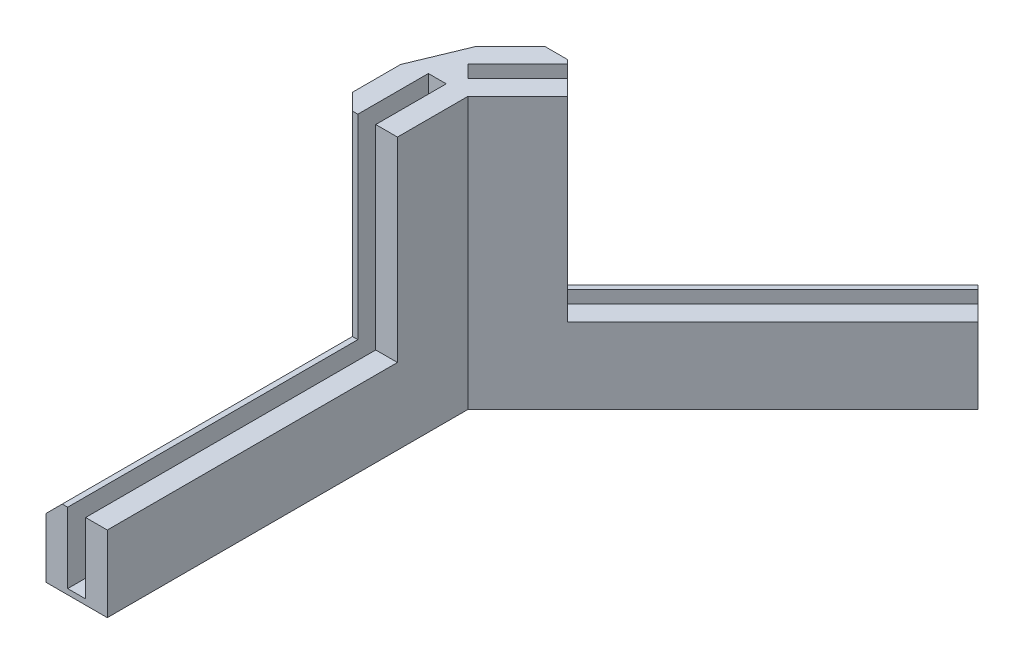
SolidWorks part; units mm, degrees
ref_plane "Front Plane" through (0, 0, 0) normal (0, 0, 1) x (1, 0, 0)
ref_plane "Top Plane" through (0, 0, 0) normal (0, 1, 0) x (1, 0, 0)
ref_plane "Right Plane" through (0, 0, 0) normal (1, 0, 0) x (0, 0, -1)
sketch "Sketch2" plane through (0, 0, 0) normal (0, 1, 0) x (1, 0, 0)
  line L0 (-1.7, -2) -> (-1.7, -15)
  line L1 (-1.7, -15) -> (-5.7, -15)
  line L2 (-5.7, -15) -> (-5.7, -2)
  line L3 (-5.7, -2) -> (-9, -2)
  line L4 (-9, -2) -> (-9, -15)
  line L5 (-9, -15) -> (-13, -15)
  line L7 (-13, -15) -> (-13, 2.6806)
  line L9 (-1.7, -2) -> (-13, 2.6806)
extrude "Boss-Extrude1" add sketch "Sketch2" along normal blind 50
sketch "Sketch3" plane through (0, 0, 2) normal (0, 0, 1) x (1, 0, 0)
  line L0 (-9, 0) -> (-9, 1)
  line L1 (-9, 50) -> (-9, 0) construction
  line L2 (-5.7, 0) -> (-5.7, 1)
  line L3 (-5.7, 50) -> (-5.7, 0) construction
  line L4 (-5.7, 1) -> (-9, 1)
  line L5 (-9, 0) -> (-5.7, 0)
extrude "Boss-Extrude2" add sketch "Sketch3" along normal up to vertex (13 mm away) up to point (-9, 0, 15)
sketch "Sketch5" plane through (0, 0, 15) normal (0, 0, 1) x (1, 0, 0)
  line L0 (-13, 0) -> (-1.7, 0)
  line L1 (-1.7, 50) -> (-1.7, 0) construction
  line L2 (-13, 0) -> (-1.7, 0) construction
  line L3 (-1.7, 0) -> (-1.7, 14)
  line L4 (-13, 0) -> (-13, 14)
  line L5 (-13, 50) -> (-13, 0) construction
  line L6 (-9, 1) -> (-9, 14)
  line L7 (-9, 50) -> (-9, 1) construction
  line L8 (-5.7, 1) -> (-5.7, 14)
  line L9 (-5.7, 50) -> (-5.7, 1) construction
  line L10 (-13, 14) -> (-9, 14)
  line L11 (-9, 1) -> (-5.7, 1)
  line L12 (-5.7, 14) -> (-1.7, 14)
extrude "Boss-Extrude3" add sketch "Sketch5" along normal blind 53.5
ref_plane "Plane1" through (-0.9561, 0, 2.3081) normal (0.3827, 0, -0.9239) x (-0.9239, 0, -0.3827)
mirror "Mirror1" about plane through (-0.9561, 0, 2.3081) normal (0.3827, 0, -0.9239) of bodies 116 117
fillet "Chamfer1" radius 14 1 edges at (-13, 25, -2.6806) type face fillet profile chamfer first side face at (-13, 21.3333, 26.9398) second side face at (7.9447, 21.3333, -23.6254)
chamfer "Chamfer2" distance 3 angle 45 4 edges at (-13, 32, 15) (-13, 14, 41.75) (18.4171, 14, -34.0978) (-0.4979, 32, -15.1827)
